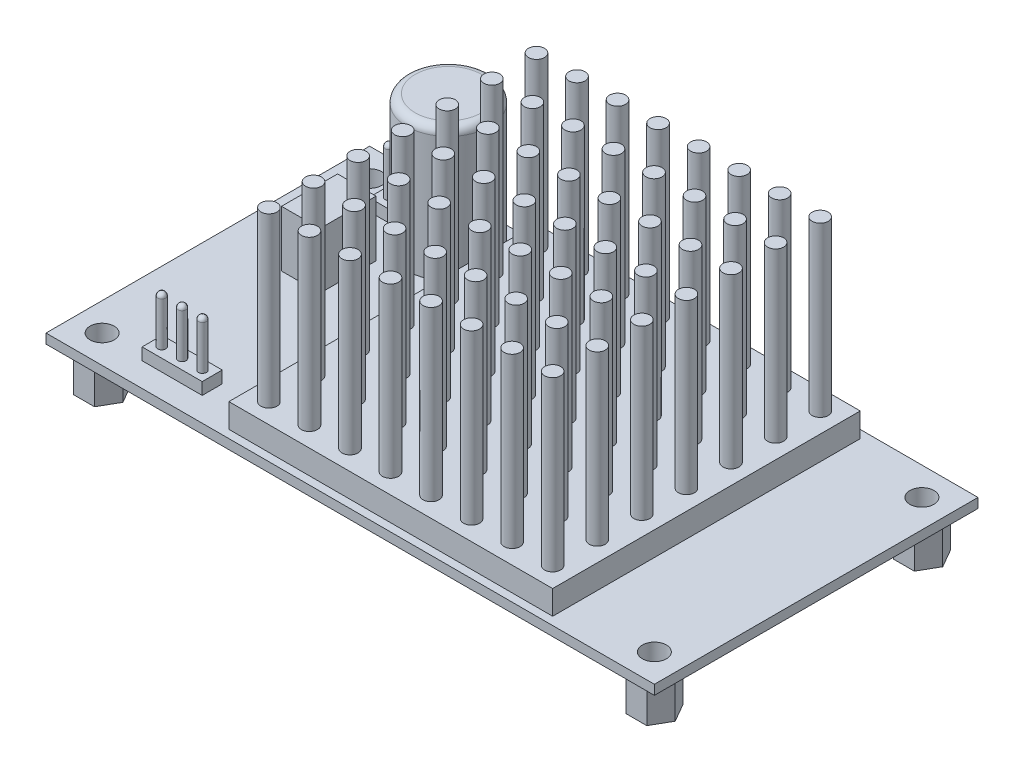
SolidWorks part; units mm, degrees
ref_plane "Front Plane" through (0, 0, 0) normal (0, 0, 1) x (1, 0, 0)
ref_plane "Top Plane" through (0, 0, 0) normal (0, 1, 0) x (1, 0, 0)
ref_plane "Right Plane" through (0, 0, 0) normal (1, 0, 0) x (0, 0, -1)
sketch "Sketch1" plane through (0, 0, 0) normal (0, 1, 0) x (1, 0, 0)
  line L1 (-37.975, -20.2) -> (37.975, -20.2)
  line L2 (-37.975, -20.2) -> (-37.975, 20.2)
  line L3 (-37.975, 20.2) -> (37.975, 20.2)
  line L4 (37.975, -20.2) -> (37.975, 20.2)
  line L5 (-37.975, -20.2) -> (37.975, 20.2) construction
  line L6 (-37.975, 20.2) -> (37.975, -20.2) construction
  line L7 (34.475, -16.7) -> (-34.475, -16.7) construction
  line L8 (34.475, -16.7) -> (34.475, 16.7) construction
  line L9 (34.475, 16.7) -> (-34.475, 16.7) construction
  line L10 (-34.475, -16.7) -> (-34.475, 16.7) construction
  line L11 (34.475, -16.7) -> (-34.475, 16.7) construction
  line L12 (34.475, 16.7) -> (-34.475, -16.7) construction
  circle A0 centre (-34.475, 16.7) radius 1.5
  circle A1 centre (34.475, 16.7) radius 1.5
  circle A2 centre (34.475, -16.7) radius 1.5
  circle A3 centre (-34.475, -16.7) radius 1.5
  point P0 (0, 0)
  point P6 (0, 0)
  dimension "D5" = 3
  dimension "D1" = 40.4
  dimension "D2" = 75.95
  dimension "D3" = 3.5
  dimension "D4" = 3.5
extrude "Boss-Extrude1" add sketch "Sketch1" along normal blind 1.2
sketch "Sketch2" plane through (0, 1.2, 0) normal (0, 1, 0) x (1, 0, 0)
  line L0 (-37.975, -20.2) -> (37.975, -20.2) construction
  line L1 (37.975, -20.2) -> (37.975, 20.2) construction
  line L2 (-37.975, 20.2) -> (-37.975, -20.2) construction
  circle A0 centre (32.895, -8.9) radius 0.5
  circle A1 centre (32.895, -6.36) radius 0.5
  circle A2 centre (32.895, -3.82) radius 0.5
  circle A3 centre (32.895, -1.28) radius 0.5
  circle A4 centre (32.895, 1.26) radius 0.5
  circle A5 centre (32.895, 3.8) radius 0.5
  circle A6 centre (32.895, 6.34) radius 0.5
  circle A7 centre (32.895, 8.88) radius 0.5
  circle A8 centre (-32.765, -11.44) radius 0.5
  circle A9 centre (-32.765, -8.9) radius 0.5
  circle A10 centre (-32.765, -6.36) radius 0.5
  circle A11 centre (-32.765, -3.82) radius 0.5
  circle A12 centre (-32.765, -1.28) radius 0.5
  circle A13 centre (-32.765, 1.26) radius 0.5
  circle A14 centre (-32.765, 3.8) radius 0.5
  circle A15 centre (-32.765, 6.34) radius 0.5
  circle A16 centre (-32.765, 8.88) radius 0.5
  circle A17 centre (-32.765, 11.42) radius 0.5
  dimension "D1" = 1
  dimension "D2" = 11.3
  dimension "D5" = 1
  dimension "D6" = 8.76
  dimension "D7" = 5.21
  dimension "D3" = 5.08
  dimension "D4" = 8
  dimension "D8" = 10
extrude "Boss-Extrude2" add sketch "Sketch2" against normal blind 5
fillet "Fillet1" radius 0.5 18 edges at (-32.765, -3.8, -8.38) (-32.765, -3.8, -5.84) (-32.765, -3.8, -3.3) (-32.765, -3.8, -0.76) (-32.765, -3.8, 1.78) (-32.765, -3.8, 4.32) (-32.765, -3.8, 6.86) (-32.765, -3.8, 9.4) (32.895, -3.8, -8.38) (32.895, -3.8, -5.84) (32.895, -3.8, -3.3) (32.895, -3.8, -0.76) (32.895, -3.8, 1.78) (32.895, -3.8, 4.32) (32.895, -3.8, 6.86) (-32.765, -3.8, 11.94) (32.895, -3.8, 9.4) (-32.765, -3.8, -10.92)
sketch "Sketch3" plane through (0, 0, 0) normal (0, -1, 0) x (-1, 0, 0)
  line L1 (-35.774, -18.95) -> (-33.176, -18.95)
  line L2 (-33.176, -18.95) -> (-31.8769, -16.7)
  line L3 (-31.8769, -16.7) -> (-33.176, -14.45)
  line L4 (-33.176, -14.45) -> (-35.774, -14.45)
  line L5 (-35.774, -14.45) -> (-37.0731, -16.7)
  line L6 (-37.0731, -16.7) -> (-35.774, -18.95)
  line L8 (0, 0) -> (0, -20.2) construction
  line L9 (37.975, -20.2) -> (-37.975, -20.2) construction
  line L10 (0, 0) -> (-37.975, 0) construction
  line L11 (-37.975, -20.2) -> (-37.975, 20.2) construction
  line L12 (37.0731, -16.7) -> (35.774, -18.95)
  line L13 (35.774, -14.45) -> (37.0731, -16.7)
  line L14 (33.176, -14.45) -> (35.774, -14.45)
  line L15 (31.8769, -16.7) -> (33.176, -14.45)
  line L16 (33.176, -18.95) -> (31.8769, -16.7)
  line L17 (35.774, -18.95) -> (33.176, -18.95)
  line L18 (35.774, 18.95) -> (33.176, 18.95)
  line L19 (33.176, 18.95) -> (31.8769, 16.7)
  line L20 (31.8769, 16.7) -> (33.176, 14.45)
  line L21 (33.176, 14.45) -> (35.774, 14.45)
  line L22 (35.774, 14.45) -> (37.0731, 16.7)
  line L23 (37.0731, 16.7) -> (35.774, 18.95)
  line L24 (-37.0731, 16.7) -> (-35.774, 18.95)
  line L25 (-35.774, 14.45) -> (-37.0731, 16.7)
  line L26 (-33.176, 14.45) -> (-35.774, 14.45)
  line L27 (-31.8769, 16.7) -> (-33.176, 14.45)
  line L28 (-33.176, 18.95) -> (-31.8769, 16.7)
  line L29 (-35.774, 18.95) -> (-33.176, 18.95)
  circle A0 centre (-34.475, -16.7) radius 2.25 construction
  circle A1 centre (34.475, -16.7) radius 2.25 construction
  circle A2 centre (34.475, 16.7) radius 2.25 construction
  circle A3 centre (-34.475, 16.7) radius 2.25 construction
  circle A4 centre (34.475, -16.7) radius 1.5
  circle A5 centre (34.475, 16.7) radius 1.5
  circle A6 centre (-34.475, -16.7) radius 1.5
  circle A7 centre (-34.475, 16.7) radius 1.5
  dimension "D1" = 4.5
extrude "Boss-Extrude3" add sketch "Sketch3" along normal blind 5
sketch "Sketch4" plane through (0, 1.2, 0) normal (0, 1, 0) x (1, 0, 0)
  line L0 (37.975, 20.2) -> (-37.975, 20.2) construction
  line L1 (-16.145, -19.2) -> (24.275, -19.2)
  line L2 (-16.145, -19.2) -> (-16.145, 19.2)
  line L3 (-16.145, 19.2) -> (24.275, 19.2)
  line L4 (24.275, -19.2) -> (24.275, 19.2)
  line L5 (-16.145, -19.2) -> (24.275, 19.2) construction
  line L6 (-16.145, 19.2) -> (24.275, -19.2) construction
  line L7 (-37.975, -20.2) -> (37.975, -20.2) construction
  line L8 (37.975, -20.2) -> (37.975, 20.2) construction
  point P0 (4.065, 0)
  dimension "D1" = 1
  dimension "D2" = 1
  dimension "D3" = 40.42
  dimension "D4" = 13.7
extrude "Boss-Extrude4" add sketch "Sketch4" along normal blind 3
sketch "Sketch5" plane through (0, 4.2, 0) normal (0, 1, 0) x (1, 0, 0)
  line L0 (-16.145, 19.2) -> (-16.145, -19.2) construction
  line L1 (24.275, 19.2) -> (-16.145, 19.2) construction
  line L2 (-16.145, -19.2) -> (24.275, -19.2) construction
  line L3 (24.275, -19.2) -> (24.275, 19.2) construction
  circle A0 centre (-13.645, 16.7) radius 1
  circle A1 centre (-8.585, 16.7) radius 1
  circle A2 centre (-3.525, 16.7) radius 1
  circle A3 centre (1.535, 16.7) radius 1
  circle A4 centre (6.595, 16.7) radius 1
  circle A5 centre (11.655, 16.7) radius 1
  circle A6 centre (16.715, 16.7) radius 1
  circle A7 centre (21.775, 16.7) radius 1
  circle A8 centre (-8.585, 11.1333) radius 1
  circle A9 centre (-3.525, 11.1333) radius 1
  circle A10 centre (1.535, 11.1333) radius 1
  circle A11 centre (6.595, 11.1333) radius 1
  circle A12 centre (11.655, 11.1333) radius 1
  circle A13 centre (16.715, 11.1333) radius 1
  circle A14 centre (21.775, 11.1333) radius 1
  circle A15 centre (-8.585, 5.5667) radius 1
  circle A16 centre (-3.525, 5.5667) radius 1
  circle A17 centre (1.535, 5.5667) radius 1
  circle A18 centre (6.595, 5.5667) radius 1
  circle A19 centre (11.655, 5.5667) radius 1
  circle A20 centre (16.715, 5.5667) radius 1
  circle A21 centre (21.775, 5.5667) radius 1
  circle A22 centre (-8.585, 0) radius 1
  circle A23 centre (-3.525, 0) radius 1
  circle A24 centre (1.535, 0) radius 1
  circle A25 centre (6.595, 0) radius 1
  circle A26 centre (11.655, 0) radius 1
  circle A27 centre (16.715, 0) radius 1
  circle A28 centre (21.775, 0) radius 1
  circle A29 centre (-8.585, -5.5667) radius 1
  circle A30 centre (-3.525, -5.5667) radius 1
  circle A31 centre (1.535, -5.5667) radius 1
  circle A32 centre (6.595, -5.5667) radius 1
  circle A33 centre (11.655, -5.5667) radius 1
  circle A34 centre (16.715, -5.5667) radius 1
  circle A35 centre (21.775, -5.5667) radius 1
  circle A36 centre (-8.585, -11.1333) radius 1
  circle A37 centre (-3.525, -11.1333) radius 1
  circle A38 centre (1.535, -11.1333) radius 1
  circle A39 centre (6.595, -11.1333) radius 1
  circle A40 centre (11.655, -11.1333) radius 1
  circle A41 centre (16.715, -11.1333) radius 1
  circle A42 centre (21.775, -11.1333) radius 1
  circle A43 centre (-8.585, -16.7) radius 1
  circle A44 centre (-3.525, -16.7) radius 1
  circle A45 centre (1.535, -16.7) radius 1
  circle A46 centre (6.595, -16.7) radius 1
  circle A47 centre (11.655, -16.7) radius 1
  circle A48 centre (16.715, -16.7) radius 1
  circle A49 centre (21.775, -16.7) radius 1
  circle A50 centre (-13.645, 11.1333) radius 1
  circle A51 centre (-13.645, 5.5667) radius 1
  circle A52 centre (-13.645, 0) radius 1
  circle A53 centre (-13.645, -5.5667) radius 1
  circle A54 centre (-13.645, -11.1333) radius 1
  circle A55 centre (-13.645, -16.7) radius 1
  dimension "D1" = 2
  dimension "D2" = 2.5
  dimension "D3" = 2.5
  dimension "D6" = 2.5
  dimension "D7" = 2.5
  dimension "D4" = 8
  dimension "D5" = 7
extrude "Boss-Extrude5" add sketch "Sketch5" along normal blind 21
sketch "Sketch7" plane through (0, 1.2, 0) normal (0, 1, 0) x (1, 0, 0)
  line L0 (37.975, 20.2) -> (-37.975, 20.2) construction
  line L1 (-16.145, 19.2) -> (-16.145, -19.2) construction
  circle A0 centre (-22.145, 14.2) radius 5.15
  dimension "D1" = 10.3
  dimension "D2" = 6
  dimension "D3" = 6
extrude "Boss-Extrude6" add sketch "Sketch7" along normal blind 16.6
fillet "Fillet2" radius 1 1 edges at (-22.145, 17.8, -9.05)
sketch "Sketch8" plane through (0, 1.2, 0) normal (0, 1, 0) x (1, 0, 0)
  line L0 (37.975, 20.2) -> (-37.975, 20.2) construction
  line L1 (-30.975, 18.2) -> (-28.475, 18.2)
  line L2 (-30.975, 18.2) -> (-30.975, 13.1)
  line L3 (-30.975, 13.1) -> (-28.475, 13.1)
  line L4 (-28.475, 18.2) -> (-28.475, 13.1)
  line L5 (-37.975, 20.2) -> (-37.975, -20.2) construction
  circle A0 centre (-29.725, 16.93) radius 0.5
  circle A1 centre (-29.725, 14.39) radius 0.5
  dimension "D5" = 1
  dimension "D6" = 2.54
  dimension "D7" = 1
  dimension "D8" = 1.27
  dimension "D1" = 2.5
  dimension "D2" = 5.1
  dimension "D3" = 2
  dimension "D4" = 9.5
extrude "Boss-Extrude7" add sketch "Sketch8" along normal blind 1.5
sketch "Sketch9" plane through (0, 2.7, 0) normal (0, 1, 0) x (1, 0, 0)
  circle A0 centre (-29.725, 16.93) radius 0.5
  circle A1 centre (-29.725, 14.39) radius 0.5
extrude "Boss-Extrude8" add sketch "Sketch9" along normal blind 6 separate body
fillet "Fillet3" radius 0.5 1 edges at (-29.725, 8.7, -13.89)
fillet "Fillet4" radius 0.5 1 edges at (-29.725, 8.7, -16.43)
sketch "Sketch10" plane through (0, 1.2, 0) normal (0, 1, 0) x (1, 0, 0)
  line L0 (-37.975, -20.2) -> (37.975, -20.2) construction
  line L1 (-28.975, -17.2) -> (-21.475, -17.2)
  line L2 (-28.975, -17.2) -> (-28.975, -14.7)
  line L3 (-28.975, -14.7) -> (-21.475, -14.7)
  line L4 (-21.475, -17.2) -> (-21.475, -14.7)
  line L5 (-37.975, 20.2) -> (-37.975, -20.2) construction
  dimension "D1" = 2.5
  dimension "D2" = 7.5
  dimension "D3" = 3
  dimension "D4" = 9
extrude "Boss-Extrude9" add sketch "Sketch10" along normal blind 1.5
sketch "Sketch11" plane through (0, 2.7, 0) normal (0, 1, 0) x (1, 0, 0)
  line L0 (-28.975, -15.95) -> (-21.475, -15.95) construction
  line L1 (-28.975, -14.7) -> (-28.975, -17.2) construction
  line L2 (-21.475, -17.2) -> (-21.475, -14.7) construction
  circle A0 centre (-27.775, -15.95) radius 0.5
  circle A1 centre (-25.235, -15.95) radius 0.5
  circle A2 centre (-22.695, -15.95) radius 0.5
  dimension "D1" = 1
  dimension "D2" = 1.2
  dimension "D3" = 3
extrude "Boss-Extrude10" add sketch "Sketch11" along normal blind 6
fillet "Fillet5" radius 0.5 3 edges at (-22.695, 8.7, 16.45) (-25.235, 8.7, 16.45) (-27.775, 8.7, 16.45)
sketch "Sketch12" plane through (0, 1.2, 0) normal (0, 1, 0) x (1, 0, 0)
  line L0 (-37.975, 20.2) -> (-37.975, -20.2) construction
  line L1 (-29.975, 8.2) -> (-25.175, 8.2)
  line L2 (-29.975, 8.2) -> (-29.975, 1.2)
  line L3 (-29.975, 1.2) -> (-25.175, 1.2)
  line L4 (-25.175, 8.2) -> (-25.175, 1.2)
  line L5 (37.975, 20.2) -> (-37.975, 20.2) construction
  dimension "D1" = 4.8
  dimension "D2" = 7
  dimension "D3" = 8
  dimension "D4" = 12
extrude "Boss-Extrude11" add sketch "Sketch12" along normal blind 7
sketch "Sketch13" plane through (0, 8.2, 0) normal (0, 1, 0) x (1, 0, 0)
  line L0 (-25.175, 8.2) -> (-29.975, 8.2) construction
  line L1 (-25.175, 1.2) -> (-25.175, 8.2) construction
  line L3 (-26.3258, 6.402) -> (-26.4242, 6.402)
  line L4 (-26.3258, 6.402) -> (-26.3258, 7.598)
  line L5 (-26.3258, 7.598) -> (-26.4242, 7.598)
  line L6 (-26.4242, 6.402) -> (-26.4242, 7.598)
  line L7 (-26.3258, 6.402) -> (-26.4242, 7.598) construction
  line L8 (-26.3258, 7.598) -> (-26.4242, 6.402) construction
  circle A0 centre (-26.375, 7) radius 0.6
  dimension "D1" = 1.2
  dimension "D2" = 1.2
  dimension "D3" = 1.2
extrude "Boss-Extrude12" add sketch "Sketch13" along normal blind 0.5 contours L6 A0 | L4 A0 region at (-26.0936, 8.2, -7) region at (-26.6564, 8.2, -7)
